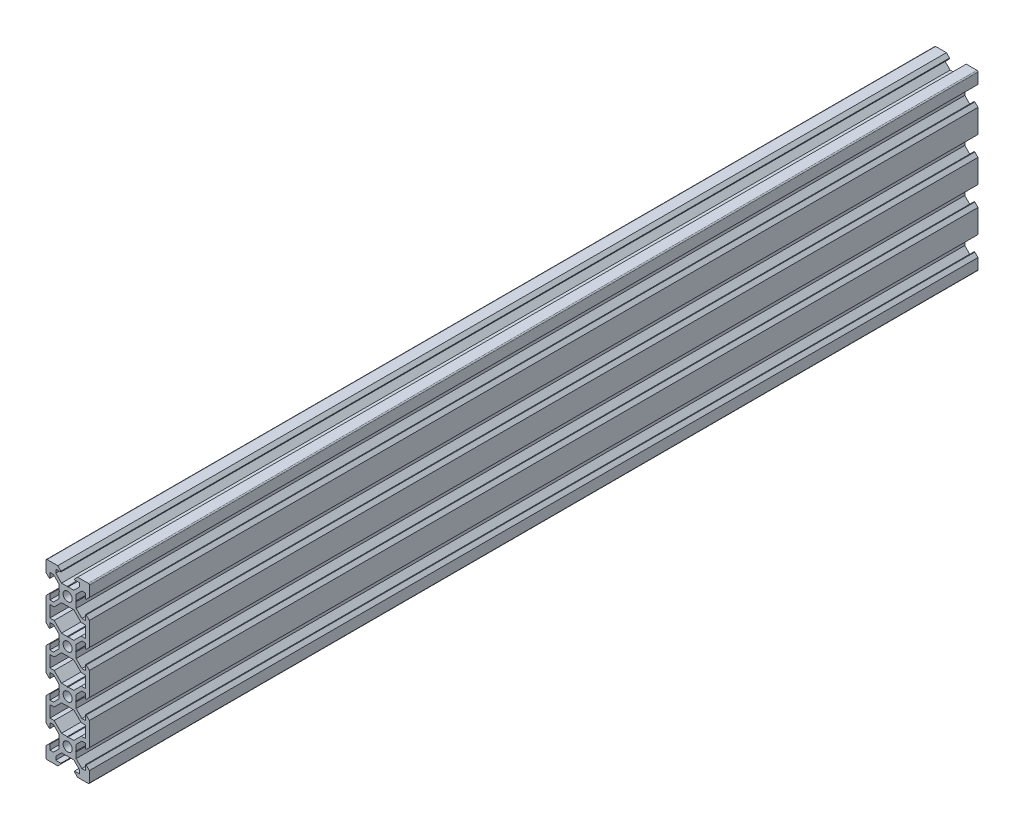
SolidWorks part; units mm, degrees
ref_plane "Plan de face" through (0, 0, 0) normal (0, 0, 1) x (1, 0, 0)
ref_plane "Plan de dessus" through (0, 0, 0) normal (0, 1, 0) x (1, 0, 0)
ref_plane "Plan de droite" through (0, 0, 0) normal (1, 0, 0) x (0, 0, -1)
ref_axis "Axe" through (0, 0, -13.782) along (0, 0, 1)
sketch "Esquisse1" plane through (0, 0, 0) normal (0, 0, 1) x (1, 0, 0)
  line L0 (0, 27.6392) -> (0, -27.6392) construction
  line L1 (-33.6074, 0) -> (33.6074, 0) construction
  line L2 (0, 0) -> (-22.2114, 22.2114) construction
  line L3 (-9.5, 10) -> (-4.58, 10)
  line L4 (-4.58, 10) -> (-3.125, 8.545)
  line L5 (-3.125, 8.545) -> (-3.125, 8.2)
  line L6 (-3.125, 8.2) -> (-5.5, 8.2)
  line L7 (-2.8393, 3.9) -> (-5.5, 6.5607)
  line L8 (-2.8393, 3.9) -> (-0.21, 3.9)
  line L9 (-5.5, 6.5607) -> (-5.5, 8.2)
  line L10 (0, 3.69) -> (0, 2.1)
  line L11 (-3.9, 2.8393) -> (-6.5607, 5.5)
  line L12 (-8.545, 3.125) -> (-8.2, 3.125)
  line L13 (-8.2, 3.125) -> (-8.2, 5.5)
  line L14 (-6.5607, 5.5) -> (-8.2, 5.5)
  line L15 (-10, 4.58) -> (-8.545, 3.125)
  line L16 (-10, 9.5) -> (-10, 4.58)
  line L17 (-0.21, 3.9) -> (0, 3.69)
  line L18 (-3.9, 2.8393) -> (-3.9, 0.21)
  line L19 (-6.2393, -12.7) -> (-8.2, -12.7)
  line L20 (-3.9, 0.21) -> (-3.69, 0)
  line L21 (-0.21, -3.9) -> (0, -3.69)
  line L22 (0, -3.69) -> (0, -2.1)
  line L23 (-6.5607, -5.5) -> (-8.2, -5.5)
  line L24 (-2.8393, -3.9) -> (-0.21, -3.9)
  line L25 (-8.545, -3.125) -> (-8.2, -3.125)
  line L26 (-10, -4.58) -> (-8.545, -3.125)
  line L27 (-8.2, -3.125) -> (-8.2, -5.5)
  line L28 (-2.8393, -3.9) -> (-6.2393, -7.3)
  line L29 (-3.9, -2.8393) -> (-6.5607, -5.5)
  line L30 (-3.9, -2.8393) -> (-3.9, -0.21)
  line L31 (-3.9, -0.21) -> (-3.69, 0)
  line L32 (-6.2393, -7.3) -> (-8.2, -7.3)
  line L33 (-8.2, -7.3) -> (-8.2, -12.7)
  line L34 (-8.2, -10) -> (-10, -10) construction
  line L35 (-10, -15.42) -> (-10, -4.58)
  line L36 (-3.9, -19.79) -> (-3.69, -20)
  line L37 (-3.9, -17.1607) -> (-3.9, -19.79)
  line L38 (-3.9, -17.1607) -> (-6.5607, -14.5)
  line L39 (-2.8393, -16.1) -> (-6.2393, -12.7)
  line L40 (-8.2, -16.875) -> (-8.2, -14.5)
  line L41 (-10, -15.42) -> (-8.545, -16.875)
  line L42 (-8.545, -16.875) -> (-8.2, -16.875)
  line L43 (-2.8393, -16.1) -> (-0.21, -16.1)
  line L44 (-6.5607, -14.5) -> (-8.2, -14.5)
  line L45 (0, -16.31) -> (0, -17.9)
  line L46 (-0.21, -16.1) -> (0, -16.31)
  line L47 (-8.2, -30) -> (-10, -30) construction
  line L48 (-3.69, -20) -> (0, -20) construction
  line L49 (-0.21, -23.9) -> (0, -23.69)
  line L50 (0, -23.69) -> (0, -22.1)
  line L51 (-6.5607, -25.5) -> (-8.2, -25.5)
  line L52 (-2.8393, -23.9) -> (-0.21, -23.9)
  line L53 (-8.545, -23.125) -> (-8.2, -23.125)
  line L54 (-10, -24.58) -> (-8.545, -23.125)
  line L55 (-8.2, -23.125) -> (-8.2, -25.5)
  line L56 (-2.8393, -23.9) -> (-6.2393, -27.3)
  line L57 (-3.9, -22.8393) -> (-6.5607, -25.5)
  line L58 (-3.9, -22.8393) -> (-3.9, -20.21)
  line L59 (-3.9, -20.21) -> (-3.69, -20)
  line L60 (-10, -24.58) -> (-10, -35.42)
  line L61 (-8.2, -32.7) -> (-8.2, -27.3)
  line L62 (-3.69, -40) -> (0, -40) construction
  line L63 (-8.2, -50) -> (-10, -50) construction
  line L64 (0, -60) -> (-22.2114, -82.2114) construction
  line L65 (-33.6074, -60) -> (33.6074, -60) construction
  line L66 (0, -87.6392) -> (0, -32.3608) construction
  line L67 (-6.2393, -32.7) -> (-8.2, -32.7)
  line L68 (-3.9, -39.79) -> (-3.69, -40)
  line L69 (-3.9, -37.1607) -> (-3.9, -39.79)
  line L70 (-3.9, -37.1607) -> (-6.5607, -34.5)
  line L71 (-2.8393, -36.1) -> (-6.2393, -32.7)
  line L72 (-8.2, -36.875) -> (-8.2, -34.5)
  line L73 (-10, -35.42) -> (-8.545, -36.875)
  line L74 (-8.545, -36.875) -> (-8.2, -36.875)
  line L75 (-6.2393, -27.3) -> (-8.2, -27.3)
  line L76 (-2.8393, -36.1) -> (-0.21, -36.1)
  line L77 (-6.5607, -34.5) -> (-8.2, -34.5)
  line L78 (0, -36.31) -> (0, -37.9)
  line L79 (-0.21, -36.1) -> (0, -36.31)
  line L80 (-0.21, -43.9) -> (0, -43.69)
  line L81 (0, -43.69) -> (0, -42.1)
  line L82 (-6.5607, -45.5) -> (-8.2, -45.5)
  line L83 (-2.8393, -43.9) -> (-0.21, -43.9)
  line L84 (-8.545, -43.125) -> (-8.2, -43.125)
  line L85 (-10, -44.58) -> (-8.545, -43.125)
  line L86 (-8.2, -43.125) -> (-8.2, -45.5)
  line L87 (-2.8393, -43.9) -> (-6.2393, -47.3)
  line L88 (-3.9, -42.8393) -> (-6.5607, -45.5)
  line L89 (-3.9, -42.8393) -> (-3.9, -40.21)
  line L90 (-3.9, -40.21) -> (-3.69, -40)
  line L91 (-10, -44.58) -> (-10, -55.42)
  line L92 (-8.2, -52.7) -> (-8.2, -47.3)
  line L93 (-6.2393, -52.7) -> (-8.2, -52.7)
  line L94 (-3.9, -59.79) -> (-3.69, -60)
  line L95 (-3.9, -57.1607) -> (-3.9, -59.79)
  line L96 (-3.9, -57.1607) -> (-6.5607, -54.5)
  line L97 (-2.8393, -56.1) -> (-6.2393, -52.7)
  line L98 (-8.2, -56.875) -> (-8.2, -54.5)
  line L99 (-10, -55.42) -> (-8.545, -56.875)
  line L100 (-8.545, -56.875) -> (-8.2, -56.875)
  line L101 (-2.8393, -56.1) -> (-0.21, -56.1)
  line L102 (-6.5607, -54.5) -> (-8.2, -54.5)
  line L103 (0, -56.31) -> (0, -57.9)
  line L104 (-0.21, -56.1) -> (0, -56.31)
  line L105 (-3.9, -60.21) -> (-3.69, -60)
  line L106 (-6.2393, -47.3) -> (-8.2, -47.3)
  line L107 (-3.9, -62.8393) -> (-3.9, -60.21)
  line L108 (-0.21, -63.9) -> (0, -63.69)
  line L109 (-10, -69.5) -> (-10, -64.58)
  line L110 (-10, -64.58) -> (-8.545, -63.125)
  line L111 (-6.5607, -65.5) -> (-8.2, -65.5)
  line L112 (-8.2, -63.125) -> (-8.2, -65.5)
  line L113 (-8.545, -63.125) -> (-8.2, -63.125)
  line L114 (-3.9, -62.8393) -> (-6.5607, -65.5)
  line L115 (0, -63.69) -> (0, -62.1)
  line L116 (-5.5, -66.5607) -> (-5.5, -68.2)
  line L117 (-2.8393, -63.9) -> (-0.21, -63.9)
  line L118 (-2.8393, -63.9) -> (-5.5, -66.5607)
  line L119 (-3.125, -68.2) -> (-5.5, -68.2)
  line L120 (-3.125, -68.545) -> (-3.125, -68.2)
  line L121 (-4.58, -70) -> (-3.125, -68.545)
  line L122 (-9.5, -70) -> (-4.58, -70)
  arc A0 (0, -2.1) -> (0, 2.1) centre (0, 0) cw
  arc A1 (-9.5, 10) -> (-10, 9.5) centre (-9.5, 9.5) ccw
  arc A2 (0, -42.1) -> (0, -37.9) centre (0, -40) cw
  arc A3 (-9.5, -70) -> (-10, -69.5) centre (-9.5, -69.5) cw
  arc A4 (0, -17.9) -> (0, -22.1) centre (0, -20) ccw
  arc A5 (0, -57.9) -> (0, -62.1) centre (0, -60) ccw
  point P4 (0, 0)
  point P7 (0, 0)
  point P30 (-10, 10)
  point P60 (0, -20)
  point P146 (-10, -70)
  dimension "D5" = 11
  dimension "D2" = 2.1
  dimension "D3" = 6.25
  dimension "D10" = 0.5
  dimension "D4" = 9.16
  dimension "D6" = 1.5
  dimension "D7" = 1.8
  dimension "D8" = 4.3
  dimension "D9" = 20
  dimension "D11" = 0.42
  dimension "D12" = 10
  dimension "D13" = 1.8
extrude "Boss.-Extru.1" add sketch "Esquisse1" along normal blind 410
sketch "Esquisse3" plane through (0, 0, 410) normal (0, 0, 1) x (1, 0, 0)
  line L0 (0, 0) -> (-9.8536, 9.8536) construction
  line L1 (-8.2, 8.2) -> (-8.2, 6.57)
  line L2 (-8.2, 6.57) -> (-7.54, 6.57)
  line L3 (-7.54, 6.57) -> (-6.57, 7.54)
  line L4 (-8.2, 3.125) -> (-8.2, 5.5) construction
  line L5 (-6.57, 8.2) -> (-6.57, 7.54)
  line L6 (-8.2, 8.2) -> (-6.57, 8.2)
  line L7 (-5.5, 6.5607) -> (-5.5, 8.2) construction
  line L8 (-10, -30) -> (6.918, -30) construction
  line L9 (-10, -24.58) -> (-10, -35.42) construction
  line L10 (-8.2, -68.2) -> (-6.57, -68.2)
  line L11 (-6.57, -68.2) -> (-6.57, -67.54)
  line L12 (-7.54, -66.57) -> (-6.57, -67.54)
  line L13 (-8.2, -66.57) -> (-7.54, -66.57)
  line L14 (-8.2, -68.2) -> (-8.2, -66.57)
  arc A0 (-9.5, 10) -> (-10, 9.5) centre (-9.5, 9.5) ccw construction
  point P13 (-7.055, 7.055)
  point P14 (-6.57, 7.87)
  point P26 (-7.055, -67.055)
  dimension "D1" = 1.07
extrude "Enlèv. mat.-Extru.1" [suppressed] cut sketch "Esquisse3" against normal through all
mirror "Symétrie1" about plane through (0, 3.69, 410) normal (-1, 0, 0) of "Enlèv. mat.-Extru.1", "Boss.-Extru.1"
